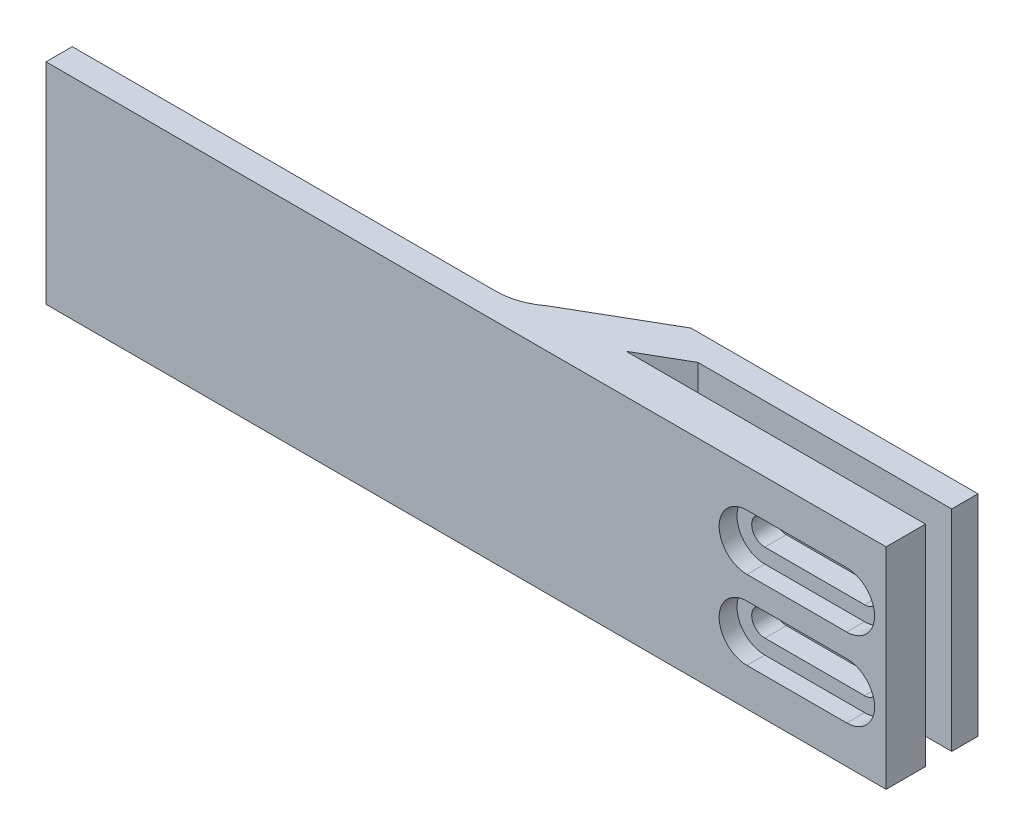
SolidWorks part; units mm, degrees
ref_plane "Front Plane" through (0, 0, 0) normal (0, 0, 1) x (1, 0, 0)
ref_plane "Top Plane" through (0, 0, 0) normal (0, 1, 0) x (1, 0, 0)
ref_plane "Right Plane" through (0, 0, 0) normal (1, 0, 0) x (0, 0, -1)
sketch "Sketch1" plane through (0, 0, 0) normal (0, 1, 0) x (1, 0, 0)
  line L0 (-36.195, -6.35) -> (-30.6957, -3.175)
  line L1 (-101.6, -6.35) -> (-45.72, -6.35)
  line L2 (-101.6, -6.35) -> (-101.6, -11.1125)
  line L3 (-101.6, -11.1125) -> (0, -11.1125)
  line L4 (0, -6.35) -> (0, -11.1125)
  line L5 (-15.4989, -6.35) -> (-22.5877, -6.35)
  line L6 (-36.195, -6.35) -> (0, -6.35)
  line L7 (-15.4989, -3.175) -> (-30.6957, -3.175)
  line L10 (-34.7215, 0) -> (-45.72, -6.35)
  line L11 (-30.6957, -3.175) -> (0, -3.175)
  line L12 (-34.7215, 0) -> (0, 0)
  line L13 (0, -3.175) -> (0, 0)
  dimension "D1" = 3.175
  dimension "D2" = 4.7625
  dimension "D3" = 101.6
  dimension "D4" = 4.7625
  dimension "D5" = 36.195
  dimension "D6" = 3.175
  dimension "D7" = 30
extrude "Boss-Extrude1" add sketch "Sketch1" along normal blind 25.4 contours L11 L13 L12 L10 L1 L2 L3 L4 L6 L5 L0 L7 region at (-44.1792, 0, 7.2065)
sketch "Sketch3" plane through (0, 0, 6.35) normal (0, 0, -1) x (-1, 0, 0)
  line L0 (101.6, 25.4) -> (101.6, 0) construction
  line L1 (101.6, 0) -> (45.72, 0)
  line L2 (101.6, 0) -> (101.6, 25.4)
  line L3 (101.6, 25.4) -> (45.72, 25.4)
  line L4 (45.72, 0) -> (45.72, 25.4)
extrude "Cut-Extrude1" cut sketch "Sketch3" against normal blind 1.5875
fillet "Fillet1" radius 7.62 1 edges at (-45.72, 12.7, 7.9375)
sketch "Sketch4" plane through (0, 0, 11.1125) normal (0, 0, 1) x (1, 0, 0)
  line L0 (-4.7625, 17.4625) -> (-16.8275, 17.4625) construction
  line L1 (-4.7625, 15.875) -> (-16.8275, 15.875)
  line L2 (-4.7625, 19.05) -> (-16.8275, 19.05)
  line L3 (-101.6, 25.4) -> (0, 25.4) construction
  line L4 (0, 12.7) -> (-41.001, 12.7) construction
  line L5 (0, 25.4) -> (0, 0) construction
  line L6 (-4.7625, 7.9375) -> (-16.8275, 7.9375) construction
  line L7 (-4.7625, 9.525) -> (-16.8275, 9.525)
  line L8 (-4.7625, 6.35) -> (-16.8275, 6.35)
  arc A0 (-4.7625, 15.875) -> (-4.7625, 19.05) centre (-4.7625, 17.4625) ccw
  arc A1 (-16.8275, 19.05) -> (-16.8275, 15.875) centre (-16.8275, 17.4625) ccw
  arc A2 (-4.7625, 9.525) -> (-4.7625, 6.35) centre (-4.7625, 7.9375) cw
  arc A3 (-16.8275, 6.35) -> (-16.8275, 9.525) centre (-16.8275, 7.9375) cw
  point P2 (-10.795, 17.4625)
  point P15 (-10.795, 7.9375)
  dimension "D1" = 3.175
  dimension "D2" = 6.35
  dimension "D3" = 12.065
  dimension "D4" = 4.7625
extrude "Cut-Extrude2" cut sketch "Sketch4" against normal up to surface (11.1125 mm away) contours L2 A1 L1 A0 | L8 A3 L7 A2 region at (-10.795, 17.4625, 11.1125) up to face at (-17.3607, 12.7, 0)
sketch "Sketch5" plane through (0, 0, 11.1125) normal (0, 0, 1) x (1, 0, 0)
  line L0 (-4.7625, 6.35) -> (-16.8275, 6.35) construction
  line L1 (-4.7625, 9.525) -> (-16.8275, 9.525) construction
  line L2 (-4.7625, 15.875) -> (-16.8275, 15.875) construction
  line L3 (-4.7625, 19.05) -> (-16.8275, 19.05) construction
  line L4 (-4.7625, 6.35) -> (-16.8275, 6.35) construction
  line L5 (-4.7625, 9.525) -> (-16.8275, 9.525) construction
  line L6 (-4.7625, 15.875) -> (-16.8275, 15.875) construction
  line L7 (-4.7625, 19.05) -> (-16.8275, 19.05) construction
  line L8 (-4.7625, 4.572) -> (-16.8275, 4.572)
  line L9 (-4.7625, 11.303) -> (-16.8275, 11.303)
  line L10 (-4.7625, 14.097) -> (-16.8275, 14.097)
  line L11 (-4.7625, 20.828) -> (-16.8275, 20.828)
  arc A0 (-16.8275, 9.525) -> (-16.8275, 6.35) centre (-16.8275, 7.9375) ccw construction
  arc A1 (-4.7625, 6.35) -> (-4.7625, 9.525) centre (-4.7625, 7.9375) ccw construction
  arc A2 (-4.7625, 15.875) -> (-4.7625, 19.05) centre (-4.7625, 17.4625) ccw construction
  arc A3 (-16.8275, 19.05) -> (-16.8275, 15.875) centre (-16.8275, 17.4625) ccw construction
  arc A4 (-16.8275, 9.525) -> (-16.8275, 6.35) centre (-16.8275, 7.9375) ccw construction
  arc A5 (-4.7625, 6.35) -> (-4.7625, 9.525) centre (-4.7625, 7.9375) ccw construction
  arc A6 (-4.7625, 15.875) -> (-4.7625, 19.05) centre (-4.7625, 17.4625) ccw construction
  arc A7 (-16.8275, 19.05) -> (-16.8275, 15.875) centre (-16.8275, 17.4625) ccw construction
  arc A8 (-16.8275, 11.303) -> (-16.8275, 4.572) centre (-16.8275, 7.9375) ccw
  arc A9 (-4.7625, 4.572) -> (-4.7625, 11.303) centre (-4.7625, 7.9375) ccw
  arc A10 (-16.8275, 20.828) -> (-16.8275, 14.097) centre (-16.8275, 17.4625) ccw
  arc A11 (-4.7625, 14.097) -> (-4.7625, 20.828) centre (-4.7625, 17.4625) ccw
  dimension "D1" = 1.778
extrude "Cut-Extrude3" cut sketch "Sketch5" against normal blind 2.159
